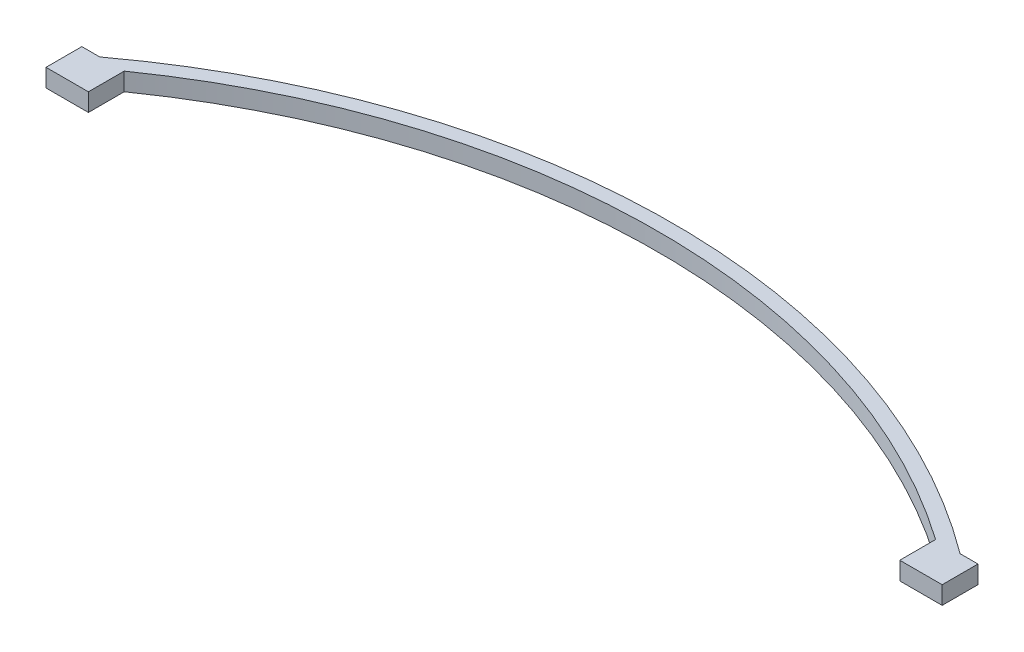
SolidWorks part; units mm, degrees
ref_plane "Front" through (0, 0, 0) normal (0, 0, 1) x (1, 0, 0)
ref_plane "Top" through (0, 0, 0) normal (0, 1, 0) x (1, 0, 0)
ref_plane "Right" through (0, 0, 0) normal (1, 0, 0) x (0, 0, -1)
sketch "Sketch1" plane through (0, 0, 0) normal (0, 1, 0) x (1, 0, 0)
  line L0 (-76.2, 0) -> (76.2, 0) construction
  line L1 (0, 0) -> (0, 25.24) construction
  line L2 (-76.2, 0) -> (-71.8642, 0)
  line L3 (71.8642, 0) -> (76.2, 0)
  arc A0 (-76.2, 0) -> (76.2, 0) centre (0, -102.4046) cw
  arc A1 (-71.8642, 0) -> (71.8642, 0) centre (0, -102.4046) cw
  arc A2 (-74.6837, -2.0377) -> (74.6837, -2.0377) centre (0, -102.4046) cw construction
  point P4 (0, 0)
  dimension "D1" = 152.4
  dimension "D2" = 25.24
  dimension "D3" = 2.54
extrude "Boss-Extrude2" add sketch "Sketch1" along normal blind 3.175
sketch "Sketch2" plane through (0, 0, 0) normal (0, 0, 1) x (1, 0, 0)
  line L0 (-76.2, 3.175) -> (-76.2, 0) construction
  line L1 (-71.8642, 3.175) -> (-79.375, 3.175)
  line L2 (-71.8642, 3.175) -> (-71.8642, 0)
  line L3 (-71.8642, 0) -> (-79.375, 0)
  line L4 (-79.375, 3.175) -> (-79.375, 0)
  line L5 (0, 98.156) -> (0, -98.156) construction
  line L7 (71.8642, 0) -> (79.375, 0)
  line L8 (79.375, 3.175) -> (79.375, 0)
  line L9 (71.8642, 3.175) -> (79.375, 3.175)
  line L10 (71.8642, 3.175) -> (71.8642, 0)
  point P11 (0, 0)
  dimension "D1" = 3.175
  dimension "D2" = 3.175
extrude "Boss-Extrude3" add sketch "Sketch2" along normal blind 6.35
